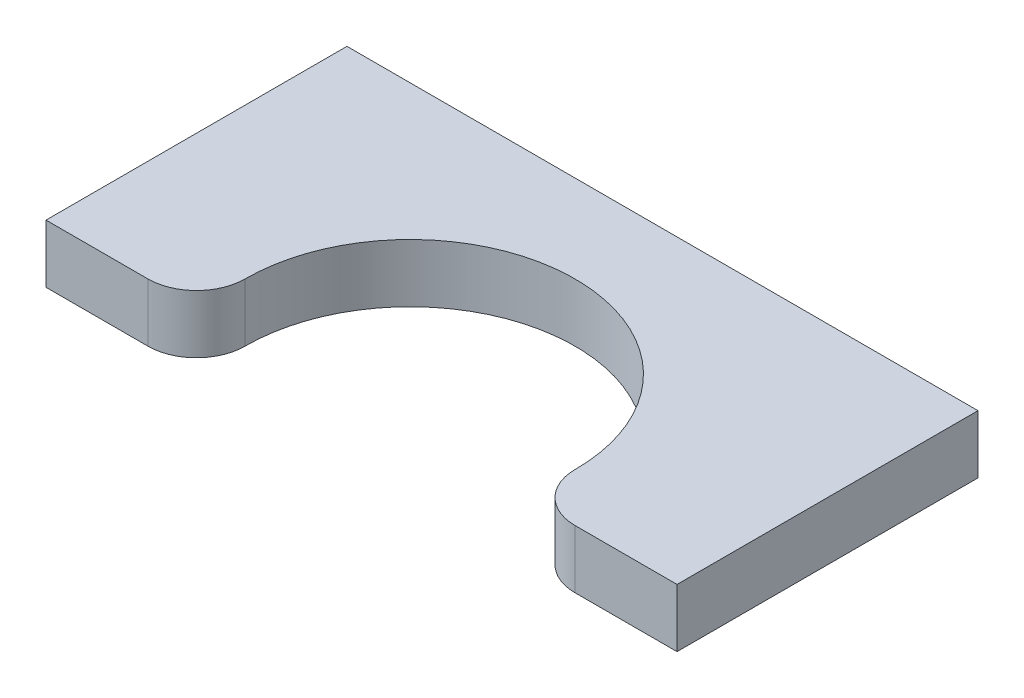
SolidWorks part; units mm, degrees
ref_plane "Front Plane" through (0, 0, 0) normal (0, 0, 1) x (1, 0, 0)
ref_plane "Top Plane" through (0, 0, 0) normal (0, 1, 0) x (1, 0, 0)
ref_plane "Right Plane" through (0, 0, 0) normal (1, 0, 0) x (0, 0, -1)
sketch "Sketch1" plane through (0, 0, 0) normal (0, 1, 0) x (1, 0, 0)
  line L0 (16.2481, -15.5) -> (32.5, -15.5)
  line L1 (-32.5, -15.5) -> (-16.2481, -15.5)
  line L2 (-32.5, -15.5) -> (-32.5, 15.5)
  line L3 (-32.5, 15.5) -> (32.5, 15.5)
  line L4 (32.5, -15.5) -> (32.5, 15.5)
  line L5 (-32.5, -15.5) -> (32.5, 15.5) construction
  line L6 (-32.5, 15.5) -> (32.5, -15.5) construction
  line L7 (0, -55) -> (0, 55) construction
  arc A0 (16.2481, -15.5) -> (-16.2481, -15.5) centre (0, -10.5) ccw
  point P0 (0, 0)
  point P7 (0, 0)
  dimension "D3" = 17
  dimension "D1" = 31
  dimension "D2" = 65
  dimension "D4" = 26
extrude "Boss-Extrude1" add sketch "Sketch1" along normal blind 3 and the other way blind 3
fillet "Fillet1" radius 5 2 edges at (16.2481, 0, 15.5) (-16.2481, 0, 15.5)
